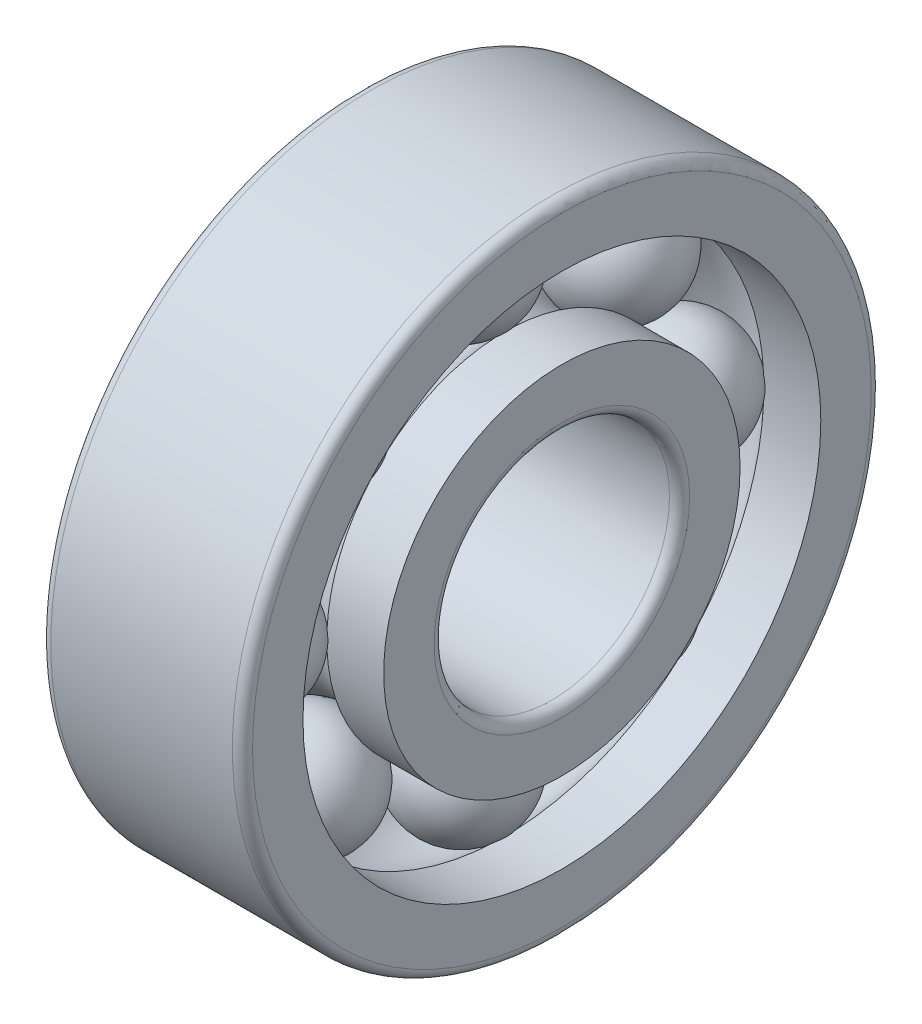
SolidWorks part; units mm, degrees
ref_plane "Plane1" through (0, 0, 0) normal (0, 0, 1) x (1, 0, 0)
ref_plane "Plane2" through (0, 0, 0) normal (0, 1, 0) x (1, 0, 0)
ref_plane "Plane3" through (0, 0, 0) normal (1, 0, 0) x (0, 0, -1)
other "Configuration Table"
sketch "Clipboard" plane through (0, 0, 0) normal (0, 0, 1) x (1, 0, 0)
  line L0 (-10, 0) -> (10, 0) construction
  line L1 (0, 0) -> (22.1431, -3.112)
  line L2 (0, 0) -> (6.4367, 0.9046)
  line L3 (0, 0) -> (22.1431, -3.112)
  line L4 (0, 0) -> (-22.3573, -0.3902)
  dimension "BallCLRad" = 6.5
sketch "CagSpiSke" plane through (0, 0, 0) normal (0, 0, 1) x (1, 0, 0)
  line L0 (0.18, 6.2) -> (0.18, 6.8)
  line L1 (0.18, 6.8) -> (-0.18, 6.8)
  line L2 (-0.18, 6.8) -> (-0.18, 6.2)
  line L3 (-0.18, 6.2) -> (0.18, 6.2)
  line L4 (-20.6375, 0) -> (20.6375, 0) construction
  line L5 (0, 0) -> (0, 23.7692) construction
  dimension "OD" = 13.6
  dimension "ID" = 12.4
revolve "CageSpine" add sketch "CagSpiSke" angle 0.001 about L4 reverse direction yes
ref_axis "Axis1" through (-50, 0, 0) along (1, 0, 0)
sketch "CagBalSke" plane through (0, 0, 0) normal (0, 0, 1) x (1, 0, 0)
  line L0 (-1.98, 6.5) -> (1.98, 6.5)
  line L1 (-1.905, 6.5) -> (1.905, 6.5) construction
  line L2 (-10, 0) -> (10, 0) construction
  line L3 (0, 0) -> (0, 24) construction
  arc A0 (1.98, 6.5) -> (-1.98, 6.5) centre (0, 6.5) cw
  dimension "BallCLRad" = 6.5
revolve "CageBall" [suppressed] add sketch "CagBalSke" angle 360 about L1 reverse direction yes
pattern_circular "CageBalls" [suppressed] count 8 every 45 about axis through (-50, 0, 0) along (1, 0, 0)
sketch "CagTrmODSke" plane through (0, 0, 0) normal (0, 0, 1) x (1, 0, 0)
  line L0 (1.981, 6.8) -> (1.981, 8.481)
  line L1 (1.981, 8.481) -> (-1.981, 8.481)
  line L2 (-1.981, 8.481) -> (-1.981, 6.8)
  line L3 (-1.981, 6.8) -> (1.981, 6.8)
  line L4 (-20.6375, 0) -> (20.6375, 0) construction
  line L5 (0, 0) -> (0, 25) construction
  dimension "Width" = 3.962
  dimension "ID" = 13.6
  dimension "OD" = 16.962
revolve "CageTrimOD" [suppressed] cut sketch "CagTrmODSke" angle 360 about L4 reverse direction yes
sketch "CagTrmIDSke" plane through (0, 0, 0) normal (0, 0, 1) x (1, 0, 0)
  line L0 (1.981, 4.521) -> (1.981, 6.2)
  line L1 (1.981, 6.2) -> (-1.981, 6.2)
  line L2 (-1.981, 6.2) -> (-1.981, 4.521)
  line L3 (-1.981, 4.521) -> (1.981, 4.521)
  line L4 (-20.6375, 0) -> (20.6375, 0) construction
  line L5 (0, 0) -> (0, 25) construction
  dimension "Width" = 3.962
  dimension "ID" = 9.042
  dimension "OD" = 12.4
revolve "CageTrimID" [suppressed] cut sketch "CagTrmIDSke" angle 360 about L4 reverse direction yes
sketch "BalSimSke" plane through (0, 0, 0) normal (0, 0, 1) x (1, 0, 0)
  line L0 (-10, 0) -> (10, 0) construction
  line L1 (-10, 6.5) -> (10, 6.5) construction
  line L2 (0, 0) -> (0, 23) construction
  circle A0 centre (0, 6.5) radius 1.8
  dimension "BallCLRad" = 6.5
  dimension "Ball_diameter" = 3.6
revolve "BallsSimplified" [suppressed] add sketch "BalSimSke" angle 360 about L0
sketch "BalDetSke" plane through (0, 0, 0) normal (0, 0, 1) x (1, 0, 0)
  line L0 (-1.8, 6.5) -> (1.8, 6.5)
  line L1 (-1.905, 6.5) -> (1.905, 6.5) construction
  line L2 (0, 0) -> (0, 25) construction
  arc A0 (1.8, 6.5) -> (-1.8, 6.5) centre (0, 6.5) cw
  dimension "BallCLRad" = 6.5
  dimension "Ball_diameter" = 3.6
revolve "BallDetailed" add sketch "BalDetSke" angle 360 about L1 reverse direction yes
sketch "InnRacSke" plane through (0, 0, 0) normal (0, 0, 1) x (1, 0, 0)
  line L0 (-1.3079, 5.3) -> (-3, 5.3)
  line L1 (-3, 5.3) -> (-3, 3.8)
  line L2 (-2.7, 3.5) -> (2.7, 3.5)
  line L3 (3, 3.8) -> (3, 5.3)
  line L4 (3, 5.3) -> (1.3079, 5.3)
  line L5 (-20.6375, 0) -> (20.6375, 0) construction
  line L6 (0, 0) -> (0, 30) construction
  arc A0 (-3, 3.8) -> (-2.7, 3.5) centre (-2.7, 3.8) ccw
  arc A1 (2.7, 3.5) -> (3, 3.8) centre (2.7, 3.8) ccw
  arc A2 (1.3079, 5.3) -> (-1.3079, 5.3) centre (0, 6.5) cw
  dimension "BallCLRad" = 6.5
  dimension "Fillet_radius" = 0.3
  dimension "Ball_diameter" = 3.55
  dimension "ID" = 7
  dimension "OD" = 10.6
  dimension "Width" = 6
revolve "InnerRace" add sketch "InnRacSke" angle 360 about L5 reverse direction yes
sketch "OutRacSke" plane through (0, 0, 0) normal (0, 0, 1) x (1, 0, 0)
  line L0 (-1.3079, 7.7) -> (-3, 7.7)
  line L1 (-3, 7.7) -> (-3, 9.2)
  line L2 (-2.7, 9.5) -> (2.7, 9.5)
  line L3 (3, 9.2) -> (3, 7.7)
  line L4 (3, 7.7) -> (1.3079, 7.7)
  line L5 (-20.6375, 0) -> (20.6375, 0) construction
  line L6 (0, 0) -> (0, 30) construction
  arc A0 (-3, 9.2) -> (-2.7, 9.5) centre (-2.7, 9.2) cw
  arc A1 (2.7, 9.5) -> (3, 9.2) centre (2.7, 9.2) cw
  arc A2 (1.3079, 7.7) -> (-1.3079, 7.7) centre (0, 6.5) ccw
  dimension "BallCLRad" = 6.5
  dimension "Fillet_radius" = 0.3
  dimension "Ball_diameter" = 3.55
  dimension "Width" = 6
revolve "OuterRace" add sketch "OutRacSke" angle 360 about L5 reverse direction yes
pattern_circular "BallsDetailed" count 8 every 45 about axis through (-50, 0, 0) along (1, 0, 0) of "BallDetailed"
equation "\"BallCLRad@Clipboard\" = ( \"OD@OutRacSke\" + \"ID@InnRacSke\" ) / 4"
equation "\"BallCLRad@BalSimSke\" = \"BallCLRad@Clipboard\""
equation "\"BallCLRad@BalDetSke\" = \"BallCLRad@Clipboard\""
equation "\"BallCLRad@InnRacSke\" = \"BallCLRad@Clipboard\""
equation "\"BallCLRad@OutRacSke\" = \"BallCLRad@Clipboard\""
equation "\"Ball_diameter@InnRacSke\" = \"Ball_diameter@BalDetSke\" - 0.05"
equation "\"Ball_diameter@OutRacSke\" = \"Ball_diameter@BalDetSke\" - 0.05"
equation "\"Ball_diameter@BalSimSke\" = \"Ball_diameter@BalDetSke\""
equation "\"Width@OutRacSke\" = \"Width@InnRacSke\""
equation "\"Fillet_radius@OutRacSke\" = \"Fillet_radius@InnRacSke\""
equation "\"Max_count@Clipboard\" = int( 3.14159265 / atn(( \"Ball_diameter@BalDetSke\" / 2) / sqr( \"BallCLRad@Clipboard\"  *  \"BallCLRad@Clipboard\" - ( \"Ball_diameter@BalDetSke\" / 2) *  ( \"Ball_diameter@BalDetSke\" / 2))))"
equation "\"Max_count@Clipboard\" = ((sgn( \"Max_count@Clipboard\" - \"Count@Clipboard\" )-1)*( \"Max_count@Clipboard\" - \"Count@Clipboard\" ))/-2+ \"Count@Clipboard\""
equation "\"Count@BallsDetailed\" = int( \"Show_count@Clipboard\" ) "
equation "\"Count@BallsDetailed\" = ((sgn( \"Count@BallsDetailed\" - \"Max_count@Clipboard\" )-1)*( \"Count@BallsDetailed\" - \"Max_count@Clipboard\" ))/-2+ \"Max_count@Clipboard\""
equation "\"Count@BallsDetailed\" = ((sgn( \"Count@BallsDetailed\" - \"Min_count@Clipboard\" )+1)*( \"Count@BallsDetailed\" - \"Min_count@Clipboard\"))/2 +\"Min_count@Clipboard\""
equation "\"Angle@BallsDetailed\" = 360.0 / \"Max_count@Clipboard\""
equation "\"BallCLRad@CagBalSke\" = \"BallCLRad@Clipboard\""
equation "\"Count@CageBalls\" = \"Count@BallsDetailed\""
equation "\"Angle@CageBalls\" = \"Angle@BallsDetailed\""
equation "\"Angle@CageSpine\" =  \"Angle@CageBalls\" * ( \"Count@CageBalls\" -1 + int( \"Count@CageBalls\" / \"Max_count@Clipboard\" ) )  + 0.001 -  int( \"Count@CageBalls\" / \"Max_count@Clipboard\" ) * 0.001"
equation "\"Angle@CageSpine\" =  \"Angle@CageSpine\" * int( \"Min_count@Clipboard\" / 2) + int(1 / \"Min_count@Clipboard\")  * 0.001"
equation "\"CageWallOD@CagBalSke\" =  \"Ball_diameter@BalDetSke\" * 1.1"
equation "\"Thickness@CagSpiSke\" =  \"Ball_diameter@BalDetSke\" * 0.1"
equation "\"OD@CagTrmODSke\" = \"BallCLRad@Clipboard\" * 2 + \"CageWallOD@CagBalSke\" + 0.002"
equation "\"ID@CagTrmODSke\" = \"BallCLRad@Clipboard\" * 2 + \"Ball_diameter@BalDetSke\" / 6"
equation "\"OD@CagTrmIDSke\" = \"BallCLRad@Clipboard\" * 2 - \"Ball_diameter@BalDetSke\" / 6"
equation "\"ID@CagTrmIDSke\" = \"BallCLRad@Clipboard\" * 2 - \"CageWallOD@CagBalSke\" + 0.002"
equation "\"OD@CagSpiSke\" = \"ID@CagTrmODSke\""
equation "\"ID@CagSpiSke\" = \"OD@CagTrmIDSke\""
equation "\"Width@CagTrmODSke\" = \"CageWallOD@CagBalSke\" + 0.002"
equation "\"Width@CagTrmIDSke\" = \"CageWallOD@CagBalSke\" + 0.002"
